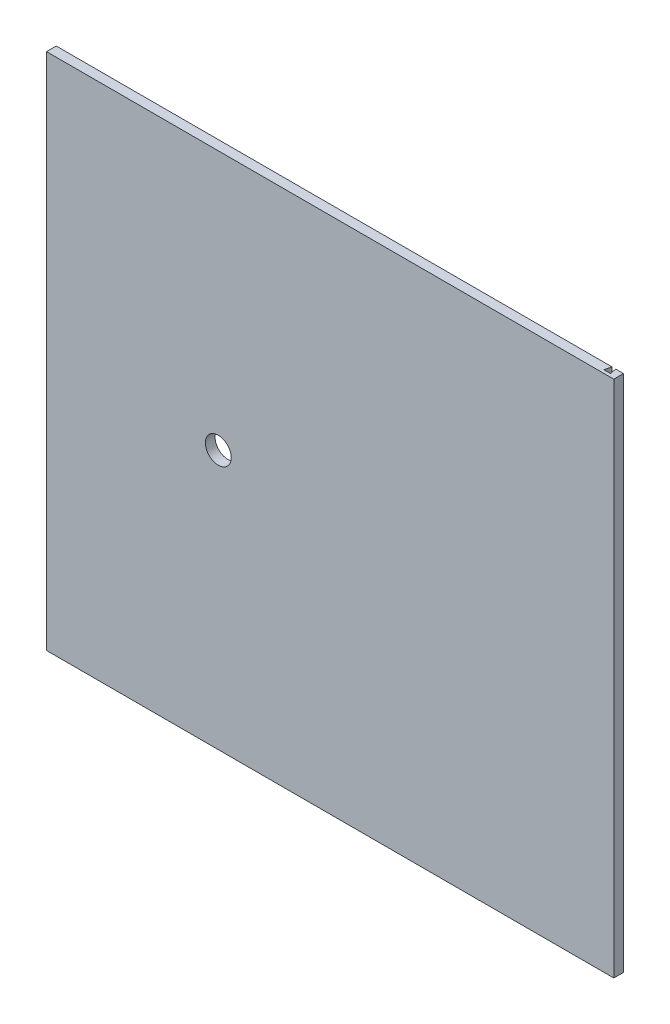
SolidWorks part; units mm, degrees
ref_plane "Front Plane" through (0, 0, 0) normal (0, 0, 1) x (1, 0, 0)
ref_plane "Top Plane" through (0, 0, 0) normal (0, 1, 0) x (1, 0, 0)
ref_plane "Right Plane" through (0, 0, 0) normal (1, 0, 0) x (0, 0, -1)
sketch "Sketch1" plane through (0, 0, 0) normal (0, 0, 1) x (1, 0, 0)
  line L1 (0, 0) -> (87.5, 0)
  line L2 (0, 0) -> (0, 80)
  line L3 (0, 80) -> (87.5, 80)
  line L4 (87.5, 0) -> (87.5, 80)
  dimension "D1" = 80
  dimension "D2" = 87.5
extrude "Boss-Extrude1" add sketch "Sketch1" along normal blind 1.5
sketch "Sketch2" plane through (0, 80, 0) normal (0, 1, 0) x (1, 0, 0)
  line L1 (86.5, -1.0071) -> (87.5, -1.0071) construction
  line L2 (86.5, -1.0071) -> (86.5, 0) construction
  line L5 (87.5, 0) -> (0, 0) construction
  line L7 (86.5, 0) -> (86.3, 0)
  line L8 (87.5, -1.5) -> (87.5, 0) construction
  line L13 (86.5, -1.0071) -> (86.3, 0)
  line L14 (86.5, -1.0071) -> (85.5, -1.0071)
  line L15 (86, -1.0071) -> (86, 0) construction
  line L17 (86.3, 0) -> (85.7, 0)
  line L18 (85.5, -1.0071) -> (85.7, 0)
  line M5 (87.5, 0) -> (0, 0)
  dimension "D1" = 1
  dimension "D2" = 0.2
  dimension "D3" = 0.5
extrude "Cut-Extrude1" cut sketch "Sketch2" against normal up to surface (80 mm away) contours L18 L14 L13 M5 region at (86, 80, 0.5455) up to face at (43.75, 0, 0.75)
sketch "Sketch3" plane through (0, 0, 1.5) normal (0, 0, 1) x (1, 0, 0)
  circle A2 centre (26.5, 40) radius 2
extrude "Cut-Extrude4" cut sketch "Sketch3" against normal up to surface (1.5 mm away) contours A2 up to face at (42.85, 40, 0)
